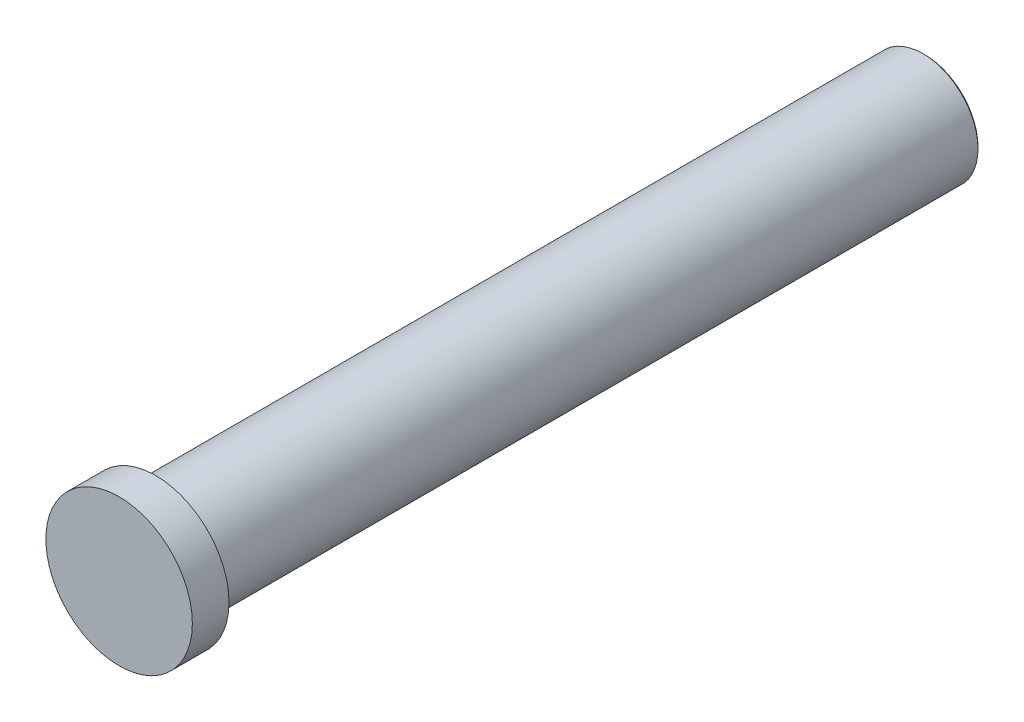
SolidWorks part; units mm, degrees
ref_plane "Front Plane" through (0, 0, 0) normal (0, 0, 1) x (1, 0, 0)
ref_plane "Top Plane" through (0, 0, 0) normal (0, 1, 0) x (1, 0, 0)
ref_plane "Right Plane" through (0, 0, 0) normal (1, 0, 0) x (0, 0, -1)
sketch "Sketch2" plane through (0, 0, 0) normal (0, 0, 1) x (1, 0, 0)
  circle A0 centre (0, 0) radius 1.5
  dimension "D1" = 3
extrude "Boss-Extrude1" add sketch "Sketch2" along normal blind 21
chamfer "Chamfer2" distance 0.05 angle 45 2 edges at (1.5, 0, 21) (1.5, 0, 0)
sketch "Sketch3" plane through (0, 0, 21) normal (0, 0, 1) x (1, 0, 0)
  circle A0 centre (0, 0) radius 2
  dimension "D1" = 4
extrude "Boss-Extrude2" add sketch "Sketch3" along normal blind 1
